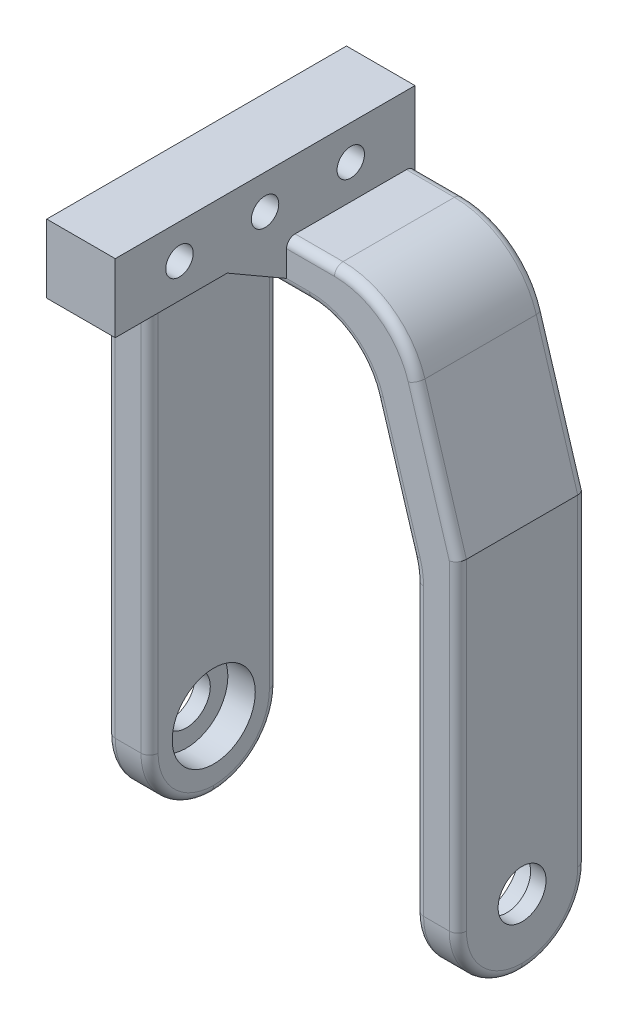
SolidWorks part; units mm, degrees
ref_plane "前视基准面" through (0, 0, 0) normal (0, 0, 1) x (1, 0, 0)
ref_plane "上视基准面" through (0, 0, 0) normal (0, 1, 0) x (1, 0, 0)
ref_plane "右视基准面" through (0, 0, 0) normal (1, 0, 0) x (0, 0, -1)
sketch "草图1" plane through (0, 0, 0) normal (0, 1, 0) x (1, 0, 0)
  line L1 (24, 7.5) -> (-17, 7.5)
  line L2 (24, 7.5) -> (24, -7.5)
  line L3 (24, -7.5) -> (-17, -7.5)
  line L4 (-17, 7.5) -> (-17, -7.5)
  line L5 (24, 7.5) -> (-17, -7.5) construction
  line L6 (24, -7.5) -> (-17, 7.5) construction
  point P0 (0, 0)
extrude "凸台-拉伸1" add sketch "草图1" against normal blind 68
sketch "草图3" plane through (0, 0, 7.5) normal (0, 0, 1) x (1, 0, 0)
  line L0 (-17, -68) -> (24, -68) construction
  line L1 (-12, -68) -> (19, -68)
  line L2 (-12, -68) -> (-12, -5)
  line L3 (-12, -5) -> (12.6087, -5)
  line L4 (19, -68) -> (19, -25.9143)
  line L5 (12.6087, -5) -> (19, -25.9143)
  line L6 (17, 0) -> (27.4891, -34.3238)
  line L7 (17, 0) -> (27.4891, 0)
  line L8 (27.4891, 0) -> (27.4891, -34.3238)
  line L9 (-17, 0) -> (24, 0) construction
  line L10 (-17, 0) -> (24, 0) construction
  point P1 (0, 0)
  point P7 (0, 0)
  point P8 (27.4891, -34.3238)
extrude "切除-拉伸1" cut sketch "草图3" against normal through all
fillet "圆角1" radius 8 3 edges at (-12, -5, 0) (19, -25.9143, 0) (12.6087, -5, 0)
fillet "圆角3" radius 7.5 4 edges at (21.5, -68, -7.5) (21.5, -68, 7.5) (-14.5, -68, -7.5) (-14.5, -68, 7.5)
sketch "草图4" plane through (24, 0, 0) normal (1, 0, 0) x (0, 0, -1)
  circle A0 centre (0, -60) radius 2.8
extrude "切除-拉伸2" cut sketch "草图4" against normal through all
sketch "草图6" plane through (19, 0, 0) normal (1, 0, 0) x (0, 0, -1)
  circle A0 centre (0, -60) radius 4.85
extrude "切除-拉伸4" cut sketch "草图6" along normal blind 3.2
ref_plane "基准面1" through (3.5, 0, 0) normal (1, 0, 0) x (0, 0, -1)
mirror "镜向2" about plane through (3.5, 0, 0) normal (1, 0, 0) of "切除-拉伸4"
sketch "草图7" plane through (0, 0, 0) normal (1, 0, 0) x (0, 0, -1)
  line L1 (-27.5, 0) -> (7.5, 0)
  line L2 (-27.5, 0) -> (-27.5, 8)
  line L3 (-27.5, 8) -> (7.5, 8)
  line L4 (7.5, 0) -> (7.5, 8)
  circle A1 centre (0, 4) radius 1.6
  circle A2 centre (-10.0079, 4) radius 1.6
  circle A3 centre (-20, 4) radius 1.6
  point P4 (-7.5, 0)
  point P5 (0, 0)
  point P6 (0, 0)
  point P7 (0, 4.6795)
  point P10 (-9.7641, 5)
  point P14 (-16.7902, 5)
  point P15 (0, 0)
  point P18 (0, 0)
  point P19 (0, 0)
  point P20 (0, 0)
  point P21 (0, 0)
  point P22 (0, 0)
  point P23 (0, 0)
  point P24 (0, 0)
  point P25 (-10.0079, 4)
  point P26 (0, 4)
  point P27 (0, 0)
  point P28 (0, 0)
  point P29 (0, 0)
  point P30 (0, 0)
  point P31 (0, 0)
extrude "凸台-拉伸2" add sketch "草图7" along normal mid plane 8
chamfer "倒角1" distance 4 angle 60 1 edges at (0, 0, 7.5) first distance on face at (5.3361, -23.1678, 7.5)
fillet "圆角4" radius 10 2 edges at (17, 0, 0) (-17, 0, 0)
fillet "圆角2" radius 1 36 edges at (-17, -35.25, -7.5) (24, -41.7031, -7.5) (24, -41.7031, 7.5) (-17, -35.25, 7.5) (-9.6569, -7.3431, 7.5) (1.3441, -5, 7.5) (19, -43.8047, 7.5) (19, -43.8047, -7.5) (1.3441, -5, -7.5) (-9.6569, -7.3431, -7.5) (-12, -36.75, -7.5) (-12, -36.75, 7.5) (19, -65.8033, 5.3033) (19, -65.8033, -5.3033) (-12, -65.8033, -5.3033) (-12, -65.8033, 5.3033) (-17, -65.8033, 5.3033) (-17, -65.8033, -5.3033) (24, -65.8033, -5.3033) (24, -65.8033, 5.3033) (11.4473, -6.5694, 7.5) (16.4949, -17.7167, 7.5) (18.9122, -25.9274, 7.5) (18.9122, -25.9274, -7.5) (16.4949, -17.7167, -7.5) (11.4473, -6.5694, -7.5) (21.5814, -14.9919, -7.5) (21.5814, -14.9919, 7.5) (6.7997, 0, -7.5) (15.5481, -1.9618, -7.5) (6.7997, 0, 7.5) (15.5481, -1.9618, 7.5) (-5.5, 0, -7.5) (-14.0711, -2.9289, -7.5) (-5.5, 0, 7.5) (-14.0711, -2.9289, 7.5)
